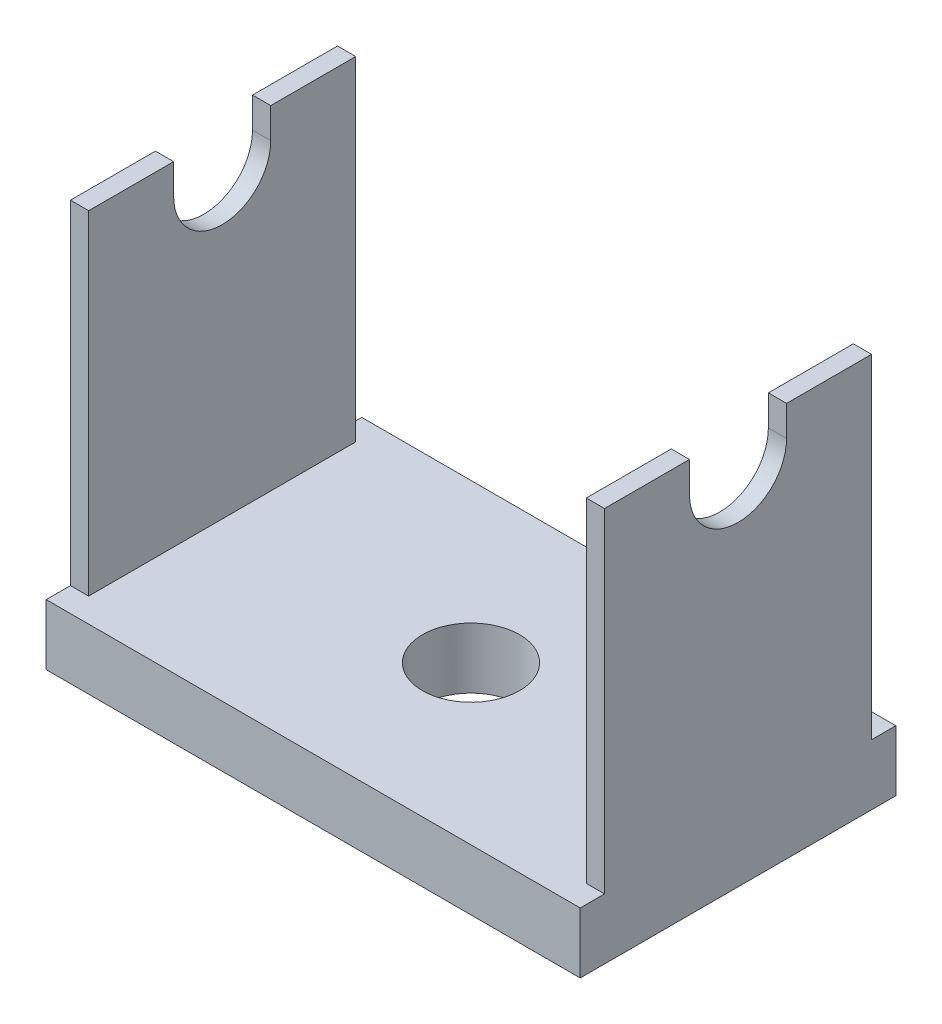
SolidWorks part; units mm, degrees
ref_plane "Front Plane" through (0, 0, 0) normal (0, 0, 1) x (1, 0, 0)
ref_plane "Top Plane" through (0, 0, 0) normal (0, 1, 0) x (1, 0, 0)
ref_plane "Right Plane" through (0, 0, 0) normal (1, 0, 0) x (0, 0, -1)
sketch "Sketch1" plane through (0, 0, 0) normal (0, 0, 1) x (1, 0, 0)
  line L0 (-22, 2.5) -> (-22, -30)
  line L1 (-22, -30) -> (22, -30)
  line L2 (22, -30) -> (22, 2.5)
  line L3 (22, 2.5) -> (20.5, 2.5)
  line L4 (20.5, 2.5) -> (20.5, -28.5)
  line L5 (20.5, -28.5) -> (-20.5, -28.5)
  line L6 (-20.5, -28.5) -> (-20.5, 2.5)
  line L7 (-20.5, 2.5) -> (-22, 2.5)
  dimension "D1" = 1.5
  dimension "D2" = 1.5
  dimension "D3" = 32.5
  dimension "D4" = 44
  dimension "D5" = 30
  dimension "D6" = 22
extrude "Boss-Extrude1" add sketch "Sketch1" against normal mid plane 22
sketch "Sketch2" plane through (0, 0, 0) normal (1, 0, 0) x (0, 0, -1)
  line L0 (-11, -30) -> (-13, -30)
  line L1 (-13, -30) -> (-13, -25)
  line L2 (-13, -25) -> (-11.5, -25)
  line L3 (-11.5, -25) -> (-11.5, -28.5)
  line L4 (-11.5, -28.5) -> (-11, -28.5)
  line L5 (-11, -30) -> (-11, 2.5) construction
  line L6 (-11, -28.5) -> (-11, -30)
  dimension "D1" = 1.5
  dimension "D2" = 0.5
  dimension "D3" = 5
extrude "Boss-Extrude2" add sketch "Sketch2" along normal mid plane 39
mirror "Mirror1" about plane through (0, 0, 0) normal (0, 0, 1) of "Boss-Extrude2"
sketch "Sketch3" plane through (0, -28.5, 0) normal (0, 1, 0) x (-1, 0, 0)
  line L0 (0, 0) -> (0, -11.5) construction
  line L1 (-19.5, -11.5) -> (19.5, -11.5) construction
  line L2 (0, 0) -> (-20.5, 0) construction
  line L3 (-20.5, -11) -> (-20.5, 11) construction
  circle A0 centre (0, 0) radius 4
  dimension "D1" = 8
extrude "Cut-Extrude1" cut sketch "Sketch3" against normal through all
sketch "Sketch4" plane through (22, 0, 0) normal (1, 0, 0) x (0, 0, -1)
  line L0 (0, 0) -> (0, 2.5) construction
  line L1 (11, 2.5) -> (-11, 2.5) construction
  line L2 (11, -30) -> (-11, -30) construction
  line L3 (-4, 0) -> (-4, 2.5)
  line L4 (-4, 2.5) -> (4, 2.5)
  line L5 (4, 2.5) -> (4, 0)
  arc A0 (-4, 0) -> (4, 0) centre (0, 0) ccw
  dimension "D2" = 4
  dimension "D1" = 30
extrude "Cut-Extrude2" cut sketch "Sketch4" against normal through all
sketch "Sketch5" plane through (0, -30, 0) normal (0, -1, 0) x (1, 0, 0)
  line L1 (-22, 13) -> (22, 13)
  line L2 (-22, 13) -> (-22, -13)
  line L3 (-22, -13) -> (22, -13)
  line L4 (22, 13) -> (22, -13)
extrude "Boss-Extrude3" add sketch "Sketch5" against normal up to surface (5 mm away) up to face at (0, -25, 12.25)
extrude "Cut-Extrude3" cut sketch "Sketch3<3>" against normal mid plane 10
sketch "Sketch3<3>" plane through (0, -28.5, 0) normal (0, 1, 0) x (-1, 0, 0) same geometry as "Sketch3"
